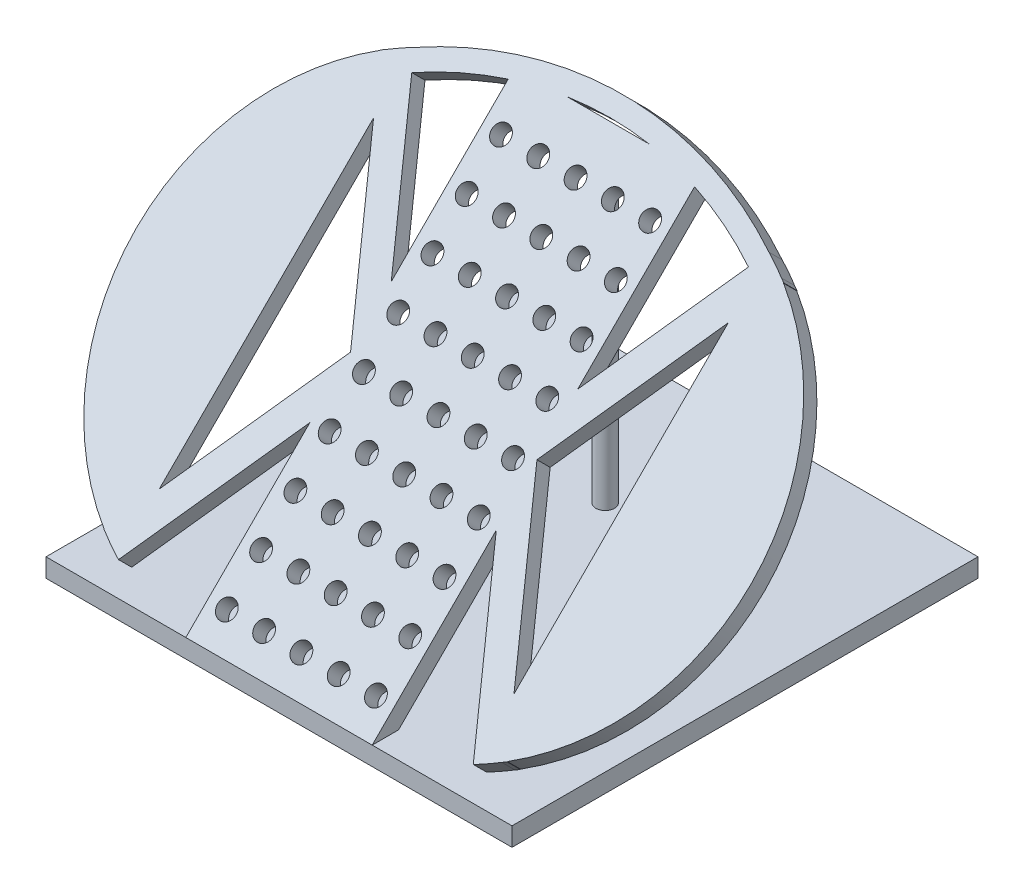
SolidWorks part; units mm, degrees
ref_plane "Front Plane" through (0, 0, 0) normal (0, 0, 1) x (1, 0, 0)
ref_plane "Top Plane" through (0, 0, 0) normal (0, 1, 0) x (1, 0, 0)
ref_plane "Right Plane" through (0, 0, 0) normal (1, 0, 0) x (0, 0, -1)
sketch "Sketch2" plane through (0, 0, 0) normal (0, 1, 0) x (1, 0, 0)
  line L1 (-31.75, 31.75) -> (31.75, 31.75)
  line L2 (-31.75, 31.75) -> (-31.75, -31.75)
  line L3 (-31.75, -31.75) -> (31.75, -31.75)
  line L4 (31.75, 31.75) -> (31.75, -31.75)
  line L5 (-31.75, 31.75) -> (31.75, -31.75) construction
  line L6 (-31.75, -31.75) -> (31.75, 31.75) construction
  point P0 (0, 0)
  dimension "D1" = 63.5
  dimension "D2" = 63.5
extrude "Boss-Extrude1" add sketch "Sketch2" along normal blind 2.54
ref_plane "Plane1" through (0, 17.145, 17.145) normal (0, 0.7071, 0.7071) x (1, 0, 0)
sketch "Sketch3" plane through (0, 17.145, 17.145) normal (0, 0.7071, 0.7071) x (1, 0, 0)
  line L0 (-31.75, -20.6546) -> (31.75, -20.6546) construction
  line L1 (0, -20.6546) -> (-12.7, -20.6546)
  line L2 (-12.7, -20.6546) -> (-12.7, 42.8454)
  line L5 (-12.7, 42.8454) -> (12.7, 42.8454)
  line L6 (12.7, 42.8454) -> (12.7, -20.6546)
  line L7 (12.7, -20.6546) -> (0, -20.6546)
  dimension "D1" = 12.7
  dimension "D2" = 63.5
  dimension "D3" = 25.4
extrude "Boss-Extrude2" add sketch "Sketch3" against normal blind 2.54
sketch "Sketch4" plane through (0, 17.145, 17.145) normal (0, 0.7071, 0.7071) x (1, 0, 0)
  line L0 (0, 42.8454) -> (0, 36.4954) construction
  line L1 (12.7, 42.8454) -> (-12.7, 42.8454) construction
  line L2 (-12.7, -20.6546) -> (12.7, -20.6546) construction
  circle A0 centre (0, 36.4954) radius 1.27
  circle A3 centre (-5.08, 36.4954) radius 1.27
  circle A4 centre (-10.16, 36.4954) radius 1.27
  circle A5 centre (5.08, 36.4954) radius 1.27
  circle A6 centre (10.16, 36.4954) radius 1.27
  circle A7 centre (-5.08, 36.4954) radius 1.27
  circle A8 centre (-10.16, 36.4954) radius 1.27
  circle A9 centre (0, 36.4954) radius 1.27
  circle A10 centre (5.08, 36.4954) radius 1.27
  circle A11 centre (-5.08, 29.8914) radius 1.27
  circle A12 centre (-10.16, 29.8914) radius 1.27
  circle A13 centre (0, 29.8914) radius 1.27
  circle A14 centre (5.08, 29.8914) radius 1.27
  circle A15 centre (-5.08, 23.2874) radius 1.27
  circle A16 centre (-10.16, 23.2874) radius 1.27
  circle A17 centre (0, 23.2874) radius 1.27
  circle A18 centre (5.08, 23.2874) radius 1.27
  circle A19 centre (-5.08, 16.6834) radius 1.27
  circle A20 centre (-10.16, 16.6834) radius 1.27
  circle A21 centre (0, 16.6834) radius 1.27
  circle A22 centre (5.08, 16.6834) radius 1.27
  circle A23 centre (-5.08, 10.0794) radius 1.27
  circle A24 centre (-10.16, 10.0794) radius 1.27
  circle A25 centre (0, 10.0794) radius 1.27
  circle A26 centre (5.08, 10.0794) radius 1.27
  circle A27 centre (-5.08, 3.4754) radius 1.27
  circle A28 centre (-10.16, 3.4754) radius 1.27
  circle A29 centre (0, 3.4754) radius 1.27
  circle A30 centre (5.08, 3.4754) radius 1.27
  circle A31 centre (-5.08, -3.1286) radius 1.27
  circle A32 centre (-10.16, -3.1286) radius 1.27
  circle A33 centre (0, -3.1286) radius 1.27
  circle A34 centre (5.08, -3.1286) radius 1.27
  circle A35 centre (-5.08, -9.7326) radius 1.27
  circle A36 centre (-10.16, -9.7326) radius 1.27
  circle A37 centre (0, -9.7326) radius 1.27
  circle A38 centre (5.08, -9.7326) radius 1.27
  circle A39 centre (-5.08, -16.3366) radius 1.27
  circle A40 centre (-10.16, -16.3366) radius 1.27
  circle A41 centre (0, -16.3366) radius 1.27
  circle A42 centre (5.08, -16.3366) radius 1.27
  circle A43 centre (0, 29.8914) radius 1.27
  circle A44 centre (-5.08, 29.8914) radius 1.27
  circle A45 centre (5.08, 29.8914) radius 1.27
  circle A46 centre (10.16, 29.8914) radius 1.27
  circle A47 centre (0, 23.2874) radius 1.27
  circle A48 centre (-5.08, 23.2874) radius 1.27
  circle A49 centre (5.08, 23.2874) radius 1.27
  circle A50 centre (10.16, 23.2874) radius 1.27
  circle A51 centre (0, 16.6834) radius 1.27
  circle A52 centre (-5.08, 16.6834) radius 1.27
  circle A53 centre (5.08, 16.6834) radius 1.27
  circle A54 centre (10.16, 16.6834) radius 1.27
  circle A55 centre (0, 10.0794) radius 1.27
  circle A56 centre (-5.08, 10.0794) radius 1.27
  circle A57 centre (5.08, 10.0794) radius 1.27
  circle A58 centre (10.16, 10.0794) radius 1.27
  circle A59 centre (0, 3.4754) radius 1.27
  circle A60 centre (-5.08, 3.4754) radius 1.27
  circle A61 centre (5.08, 3.4754) radius 1.27
  circle A62 centre (10.16, 3.4754) radius 1.27
  circle A63 centre (0, -3.1286) radius 1.27
  circle A64 centre (-5.08, -3.1286) radius 1.27
  circle A65 centre (5.08, -3.1286) radius 1.27
  circle A66 centre (10.16, -3.1286) radius 1.27
  circle A67 centre (0, -9.7326) radius 1.27
  circle A68 centre (-5.08, -9.7326) radius 1.27
  circle A69 centre (5.08, -9.7326) radius 1.27
  circle A70 centre (10.16, -9.7326) radius 1.27
  circle A71 centre (0, -16.3366) radius 1.27
  circle A72 centre (-5.08, -16.3366) radius 1.27
  circle A73 centre (5.08, -16.3366) radius 1.27
  circle A74 centre (10.16, -16.3366) radius 1.27
  point P16 (0, 0)
  point P153 (0, 0)
  dimension "D2" = 2.54
  dimension "D7" = 52.832
  dimension "D1" = 6.35
  dimension "D8" = 20.32
  dimension "D9" = 4.318
  dimension "D10" = 5.08
  dimension "D11" = 6.604
  dimension "D4" = 3
  dimension "D3" = 3
  dimension "D6" = 2
  dimension "D5" = 9
extrude "Cut-Extrude1" cut sketch "Sketch4" against normal blind 2.54 contours A13 | A11 | A12 | A15 | A23 | A25 | A26 | A58 | A42 | A4 | A3 | A0 | A5 | A6 | A46 | A14 | A16 | A17 | A18 | A50 | A54 | A22 | A21 | A19 | A20 | A24 | A62 | A30 | A29 | A27 | A28 | A32 | A31 | A33 | A34 | A66 | A70 | A38 | A37 | A35 | A36 | A40 | A39 | A41 | A74 region at (-5.08, 38.2814, -3.9914) region at (-10.16, 38.2814, -3.9914) region at (0, 38.2814, -3.9914) region at (-5.08, 33.6117, 0.6783) region at (-5.08, 24.2722, 10.0178) region at (0, 24.2722, 10.0178) region at (5.08, 24.2722, 10.0178) region at (5.08, 5.5933, 28.6967) region at (10.16, 24.2722, 10.0178)
sketch "Sketch5" plane through (0, 17.145, 17.145) normal (0, 0.7071, 0.7071) x (1, 0, 0)
  line L0 (12.7, 11.0954) -> (27.5024, 37.7397)
  line L1 (12.7, -20.6546) -> (12.7, 42.8454) construction
  line L2 (27.5024, 37.7397) -> (24.1719, 39.59)
  line L3 (24.1719, 39.59) -> (12.7, 18.9407)
  line L4 (12.7, 18.9407) -> (12.7, 11.0954)
  line L5 (12.7, 11.0954) -> (27.5003, -15.5501)
  line L6 (27.5003, -15.5501) -> (24.1702, -17.3998)
  line L7 (24.1702, -17.3998) -> (12.7, 3.2505)
  line L8 (12.7, 3.2505) -> (12.7, 11.0954)
  line L9 (12.7, 18.9407) -> (12.7, 3.2505)
  point P4 (0, 0)
  line M55 (12.7, -20.6546) -> (12.7, 42.8454)
  dimension "D1" = 30.48
  dimension "D2" = 3.81
  dimension "D3" = 23.622
  dimension "D4" = 150.95
  dimension "D5" = 30.48
  dimension "D6" = 23.622
extrude "Boss-Extrude3" add sketch "Sketch5" against normal blind 2.54 contours L2 L3 L0 M55 | L7 L6 L5 M55 region at (19.3037, 36.0524, -1.7624) region at (19.3028, 13.9287, 20.3613)
sketch "Sketch6" plane through (0, 17.145, 17.145) normal (0, 0.7071, 0.7071) x (1, 0, 0)
  line L0 (-12.7, 11.0954) -> (-27.5003, 37.7409)
  line L1 (-12.7, 42.8454) -> (-12.7, -20.6546) construction
  line L3 (-27.5003, 37.7409) -> (-24.1696, 39.5909)
  line L4 (-24.1696, 39.5909) -> (-12.6994, 18.9407)
  line L5 (-12.6994, 18.9407) -> (-12.7, 11.0954)
  line L6 (-12.7, 11.0954) -> (-27.5024, -15.5489)
  line L7 (-27.5024, -15.5489) -> (-24.1719, -17.3992)
  line L8 (-24.1719, -17.3992) -> (-12.7, 3.2501)
  line L9 (-12.7, 3.2501) -> (-12.7, 11.0954)
  dimension "D1" = 150.95
  dimension "D2" = 30.48
  dimension "D3" = 3.81
  dimension "D4" = 23.622
  dimension "D5" = 150.95
  dimension "D6" = 30.48
  dimension "D7" = 3.81
extrude "Boss-Extrude4" add sketch "Sketch6" against normal blind 2.54 contours L5 L4 L3 L0 | L8 L9 L6 L7 region at (-19.3025, 36.0527, -1.7627) region at (-19.3037, 13.9289, 20.3611)
sketch "Sketch7" plane through (0, 17.145, 17.145) normal (0, 0.7071, 0.7071) x (1, 0, 0)
  line L9 (27.5003, -15.5501) -> (24.1702, -17.3998) construction
  line L10 (-24.1719, -17.3992) -> (-24.1696, 39.5909)
  line L12 (24.1719, 39.59) -> (24.1719, -17.3989)
  line L13 (-24.1696, 39.5909) -> (24.1719, 39.59)
  arc A1 (24.1719, 39.59) -> (24.1719, -17.3989) centre (10.1672, 11.0956) cw
  arc A2 (-24.1696, 39.5909) -> (-24.1719, -17.3992) centre (-10.1674, 11.0953) ccw
  arc A3 (-24.1696, 39.5909) -> (24.1719, 39.59) centre (0.0003, -5.0908) cw
  point P1 (0, 0)
  dimension "D1" = 31.75
  dimension "D2" = 50.8
  dimension "D3" = 31.75
extrude "Extrude-Thin1" add sketch "Sketch7" against normal blind 2.54 thin contours A3 thin type one direction wall 2.54
extrude "Boss-Extrude10" add sketch "Sketch7<6>" against normal blind 2.54 contours L10 A2 | A1 L12 region at (-31.4727, 24.9912, 9.2988) region at (31.4733, 24.9908, 9.2992)
sketch "Sketch7<6>" plane through (0, 17.145, 17.145) normal (0, 0.7071, 0.7071) x (1, 0, 0) same geometry as "Sketch7"
sketch "Sketch8" plane through (0, 2.54, 0) normal (0, 1, 0) x (1, 0, 0)
  line L0 (0, 31.75) -> (0, 12.7) construction
  line L1 (31.75, 31.75) -> (-31.75, 31.75) construction
  circle A0 centre (0, 12.7) radius 1.27
  dimension "D2" = 2.54
  dimension "D1" = 19.05
extrude "Boss-Extrude11" add sketch "Sketch8" along normal blind 42.418 contours A0
